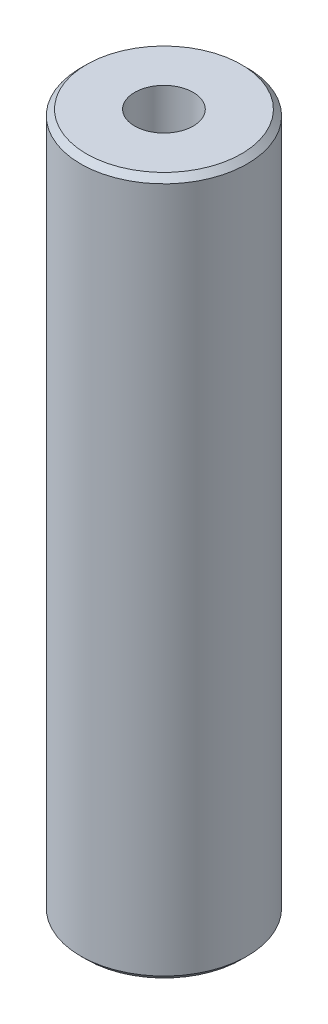
SolidWorks part; units mm, degrees
ref_plane "Front Plane" through (0, 0, 0) normal (0, 0, 1) x (1, 0, 0)
ref_plane "Top Plane" through (0, 0, 0) normal (0, 1, 0) x (1, 0, 0)
ref_plane "Right Plane" through (0, 0, 0) normal (1, 0, 0) x (0, 0, -1)
sketch "Sketch1" plane through (0, 0, 0) normal (0, 1, 0) x (1, 0, 0)
  circle A0 centre (0, 0) radius 55
  dimension "SHAFT_OD" = 110
extrude "Boss-Extrude1" add sketch "Sketch1" along normal blind 461.053
sketch "Sketch2" plane through (0, 0, 0) normal (0, 1, 0) x (1, 0, 0)
  circle A0 centre (0, 0) radius 19.3322
  dimension "BORE_D" = 38.6645
extrude "Cut-Extrude1" cut sketch "Sketch2" along normal through all
chamfer "Chamfer1" distance 3.836 angle 45 2 edges at (0, 461.053, 55) (0, 0, 55)
